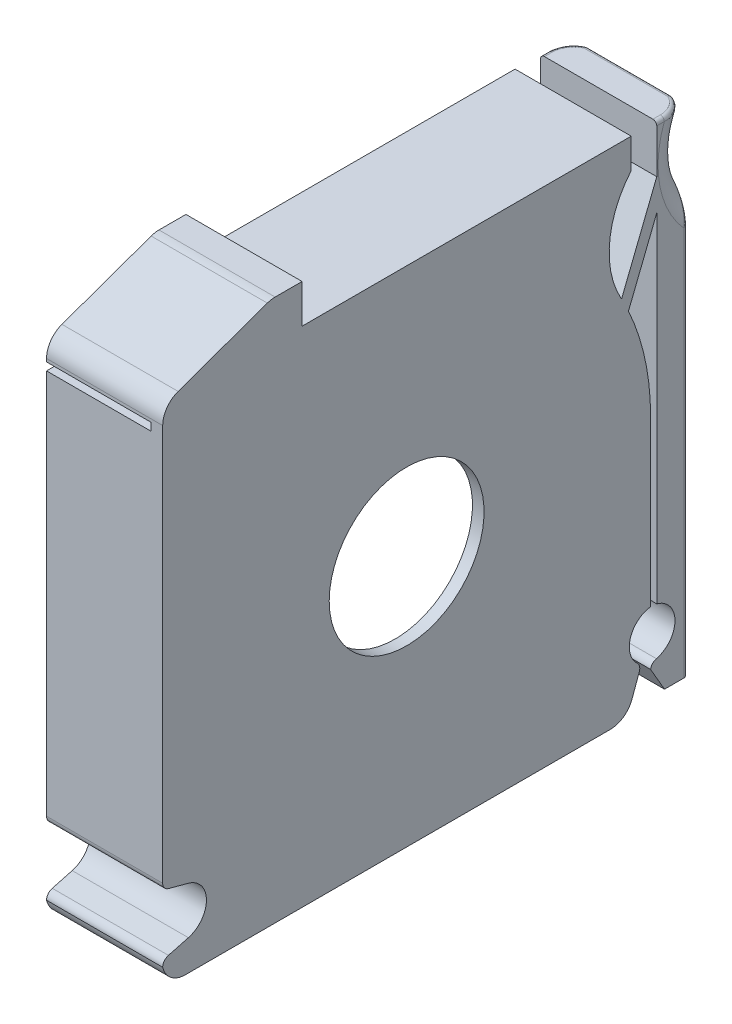
SolidWorks part; units mm, degrees
ref_plane "Plan de face" through (0, 0, 0) normal (0, 0, 1) x (1, 0, 0)
ref_plane "Plan de dessus" through (0, 0, 0) normal (0, 1, 0) x (1, 0, 0)
ref_plane "Plan de droite" through (0, 0, 0) normal (1, 0, 0) x (0, 0, -1)
sketch "Esquisse1" plane through (0, 0, 0) normal (1, 0, 0) x (0, 0, -1)
  line L0 (-31.5, 32.5) -> (31.5, -32.5) construction
  line L1 (-31.5, 32.5) -> (31.5, 32.5)
  line L2 (-31.5, 32.5) -> (-31.5, -32.5)
  line L3 (-31.5, -32.5) -> (31.5, -32.5)
  line L4 (31.5, 32.5) -> (31.5, -32.5)
  point P4 (0, 0)
  dimension "D1" = 65
  dimension "D2" = 63
extrude "Boss.-Extru.1" add sketch "Esquisse1" against normal blind 15
sketch "Esquisse2" plane through (-15, 0, 0) normal (-1, 0, 0) x (0, 0, 1)
  circle A0 centre (0, 0) radius 30
  dimension "D1" = 60
extrude "Enlèv. mat.-Extru.1" cut sketch "Esquisse2" against normal blind 13.5
sketch "Esquisse3" plane through (-15, 0, 0) normal (-1, 0, 0) x (0, 0, 1)
  line L0 (31.5, 32.5) -> (31.5, -32.5) construction
  line L1 (0, 30) -> (31.5, 30)
  line L2 (0, 30) -> (0, 29)
  line L3 (0, 29) -> (31.5, 29)
  line L4 (31.5, 30) -> (31.5, 29)
  circle A0 centre (0, 0) radius 30 construction
  circle A1 centre (0, 0) radius 30 construction
  dimension "D1" = 1
extrude "Enlèv. mat.-Extru.2" cut sketch "Esquisse3" against normal up to surface (13.5 mm away) up to face at (-1.5, 0, 30)
sketch "Esquisse4" plane through (0, 0, 0) normal (1, 0, 0) x (0, 0, -1)
  line L1 (-13.5, 37.5) -> (-13.5, 32.5)
  line L2 (31.5, 32.5) -> (-31.5, 32.5) construction
  line L3 (-13.5, 32.5) -> (-31.5, 32.5)
  line L4 (-13.5, 37.5) -> (-17.5, 37.5)
  line L5 (-17.5, 37.5) -> (-31.5, 32.5)
  dimension "D1" = 5
  dimension "D2" = 18
  dimension "D3" = 4
extrude "Boss.-Extru.2" add sketch "Esquisse4" against normal blind 15
sketch "Esquisse5" plane through (-15, 0, 0) normal (-1, 0, 0) x (0, 0, 1)
  line L0 (13.5, 35.5) -> (17, 35.5)
  line L1 (13.5, 32.5) -> (13.5, 37.5) construction
  line L2 (17.8288, 32.7498) -> (13.6811, 30)
  line L3 (0, 30) -> (31.5, 30) construction
  line L4 (13.5, 37.5) -> (17.5, 37.5) construction
  line L5 (13.5, 32.5) -> (9.7291, 30)
  line L6 (9.7291, 30) -> (13.6811, 30)
  line L7 (13.5, 35.5) -> (13.5, 32.5)
  arc A0 (17, 35.5) -> (17.8288, 32.7498) centre (17, 34) cw
  point P11 (15.5, 37.5)
  dimension "D1" = 1.5
  dimension "D2" = 2
  dimension "D3" = 6
  dimension "D4" = 3.5
extrude "Enlèv. mat.-Extru.3" cut sketch "Esquisse5" against normal up to surface (13.5 mm away) up to face at (-1.5, 14.6878, 15.7419)
sketch "Esquisse7" plane through (-15, 0, 0) normal (-1, 0, 0) x (0, 0, 1)
  line L1 (31.5, -32.5) -> (-31.5, -32.5) construction
  line L2 (31.5, 29) -> (31.5, -32.5) construction
  line L3 (28.1847, -22.4573) -> (31.5, -21.569)
  line L4 (31.5, -21.569) -> (31.5, -29.431)
  line L5 (31.5, -29.431) -> (28.1847, -28.5427)
  arc A0 (28.1847, -22.4573) -> (28.1847, -28.5427) centre (29, -25.5) ccw
  point P12 (31.5, -25.5)
  dimension "D2" = 6.3
  dimension "D1" = 7
  dimension "D3" = 2.5
  dimension "D4" = 30
extrude "Enlèv. mat.-Extru.4" cut sketch "Esquisse7" against normal through all
sketch "Esquisse8" plane through (-15, 0, 0) normal (-1, 0, 0) x (0, 0, 1)
  line L0 (-31.5, -32.5) -> (-31.5, 32.5) construction
  line L1 (-31.5, 0) -> (-35.0374, 0)
  line L2 (-35.0374, 0) -> (-35.0374, 30.5)
  line L4 (-31.5, 32.5) -> (13.5, 32.5) construction
  line L5 (-29, 32.5) -> (-29, 28.6507)
  line L6 (-29, 32.5) -> (-29, 34.0812)
  line L7 (-29, 34.0812) -> (-35.0374, 34.0812)
  line L8 (-35.0374, 34.0812) -> (-35.0374, 30.5)
  arc A0 (-27.6993, 15) -> (-31.5, 0) centre (0, 0) ccw
  arc A1 (-27.6993, 15) -> (-29, 28.6507) centre (-38.1537, 20.8912) ccw
  dimension "D3" = 12
  dimension "D1" = 2.5
  dimension "D2" = 15
extrude "Enlèv. mat.-Extru.5" cut sketch "Esquisse8" against normal through all
sketch "Esquisse9" plane through (0, 0, 0) normal (1, 0, 0) x (0, 0, -1)
  line L0 (29, 32.5) -> (-13.5, 32.5) construction
  line L1 (36.3, 32.5) -> (32.3, 32.5)
  line L2 (36.3, 32.5) -> (36.3, 31.5)
  line L3 (36.3, -31.5) -> (33.3, -31.5)
  line L4 (32.3, 32.5) -> (32.3, 26.3161)
  line L5 (-31.5, -32.5) -> (31.5, -32.5) construction
  line L6 (31.5, -32.5) -> (31.5, 0) construction
  line L7 (32.3, 26.3161) -> (27.7492, 14.9074)
  line L8 (27.7492, 14.9074) -> (28.6449, 13.1043)
  line L9 (28.6449, 13.1043) -> (32.3, 22.2675)
  line L10 (32.3, 22.2675) -> (32.3, -26.5)
  line L11 (36.3, 23.5) -> (36.3, -31.5)
  line L12 (33.3, -31.5) -> (30.4132, -26.5)
  line L13 (30.4132, -26.5) -> (32.3, -26.5)
  arc A1 (31.5, 0) -> (27.6993, 15) centre (0, 0) ccw construction
  arc A2 (36.3, 31.5) -> (36.3, 23.5) centre (45.4652, 27.5) ccw
  dimension "D7" = 10
  dimension "D1" = 3
  dimension "D2" = 1
  dimension "D3" = 0.8
  dimension "D4" = 1.5
  dimension "D5" = 1
  dimension "D6" = 8
  dimension "D8" = 4
  dimension "D9" = 120
  dimension "D10" = 5
extrude "Boss.-Extru.3" add sketch "Esquisse9" against normal blind 15
sketch "Esquisse10" plane through (-15, 0, 0) normal (-1, 0, 0) x (0, 0, 1)
  line L1 (-31.5, -32.5) -> (-31.5, -28.3823) construction
  line L2 (31.5, -32.5) -> (-31.5, -32.5) construction
  line L3 (-31.5, -21.3755) -> (-31.5, -27.458)
  line L4 (-30.3, -27.2134) -> (-28.3758, -32.5)
  line L5 (-28.3758, -32.5) -> (-31.5, -32.5)
  line L6 (-31.5, -32.5) -> (-31.5, -27.458)
  arc A1 (-30.3, -27.2134) -> (-31.5, -21.3755) centre (-31.9, -24.5) ccw
  dimension "D1" = 6.3
  dimension "D2" = 0.4
  dimension "D3" = 8
  dimension "D4" = 20
  dimension "D5" = 1.2
extrude "Enlèv. mat.-Extru.6" cut sketch "Esquisse10" against normal through all
sketch "Esquisse11" plane through (-15, 0, 0) normal (-1, 0, 0) x (0, 0, 1)
  line L0 (31.5, -32.5) -> (-28.3758, -32.5) construction
  line L1 (-32.3, 22.2675) -> (-32.3, -26.5) construction
  line L2 (-32.3, -26.5) -> (-31.5, -26.5) construction
  line L3 (-32.3, -26.5) -> (-31.5, -26.5)
  line L4 (-32.3, -21.4533) -> (-32.3, -26.5)
  line L5 (-31.5, -26.5) -> (-31.5, -27.65)
  arc A0 (-32.3, -21.4533) -> (-31.5, -27.65) centre (-31.5, -24.5) ccw
  dimension "D1" = 6.3
  dimension "D2" = 8
  dimension "D3" = 0.8
extrude "Enlèv. mat.-Extru.7" cut sketch "Esquisse11" against normal through all
sketch "Esquisse14" plane through (-15, 0, 0) normal (-1, 0, 0) x (0, 0, 1)
  arc A0 (-32.3, -21.4533) -> (-31.5, -27.65) centre (-31.5, -24.5) ccw construction
  arc A1 (-32.3, -21.4533) -> (-31.5, -27.65) centre (-31.5, -24.5) ccw construction
  point P0 (-31.5, -24.5)
  point P1 (-31.5, -24.5)
fillet "Congé1" radius 1 2 edges at (-7.5, -29.431, 31.5) (-7.5, -21.569, 31.5)
fillet "Congé2" radius 3 5 edges at (-7.5, -32.5, -28.3758) (-8.25, 30, 9.7291) (-7.5, 37.5, 17.5) (-7.5, 32.5, 31.5) (-7.5, -32.5, 31.5)
fillet "Congé3" radius 3 2 edges at (0, 27.5, -35.4652) (-15, 27.5, -35.4652)
fillet "Congé4" radius 0.5 13 edges at (-12.4572, 31.5868, -36.3) (-2.0279, 31.889, -36.3) (-0.2016, 32.5, -34.6457) (-14.347, 32.5, -35.5198) (-7.5, 31.5, -36.3) (0, 32.5, -32.8826) (-7.5, 32.5, -36.3) (-15, 32.5, -32.8826) (-15, -6.6098, -36.3) (-13.5507, 22.5176, -36.3) (0, -6.6098, -36.3) (-2.0184, 23.1034, -36.3) (-7.5, 23.5, -36.3)
fillet "Congé5" radius 1 2 edges at (-7.5, -27.2134, -30.3) (-7.5, -27.65, -31.5)
sketch "Esquisse15" plane through (-1.5, 0, 0) normal (-1, 0, 0) x (0, 0, 1)
  circle A0 centre (0, 0) radius 10
  dimension "D1" = 20
extrude "Enlèv. mat.-Extru.8" cut sketch "Esquisse15" against normal through all
